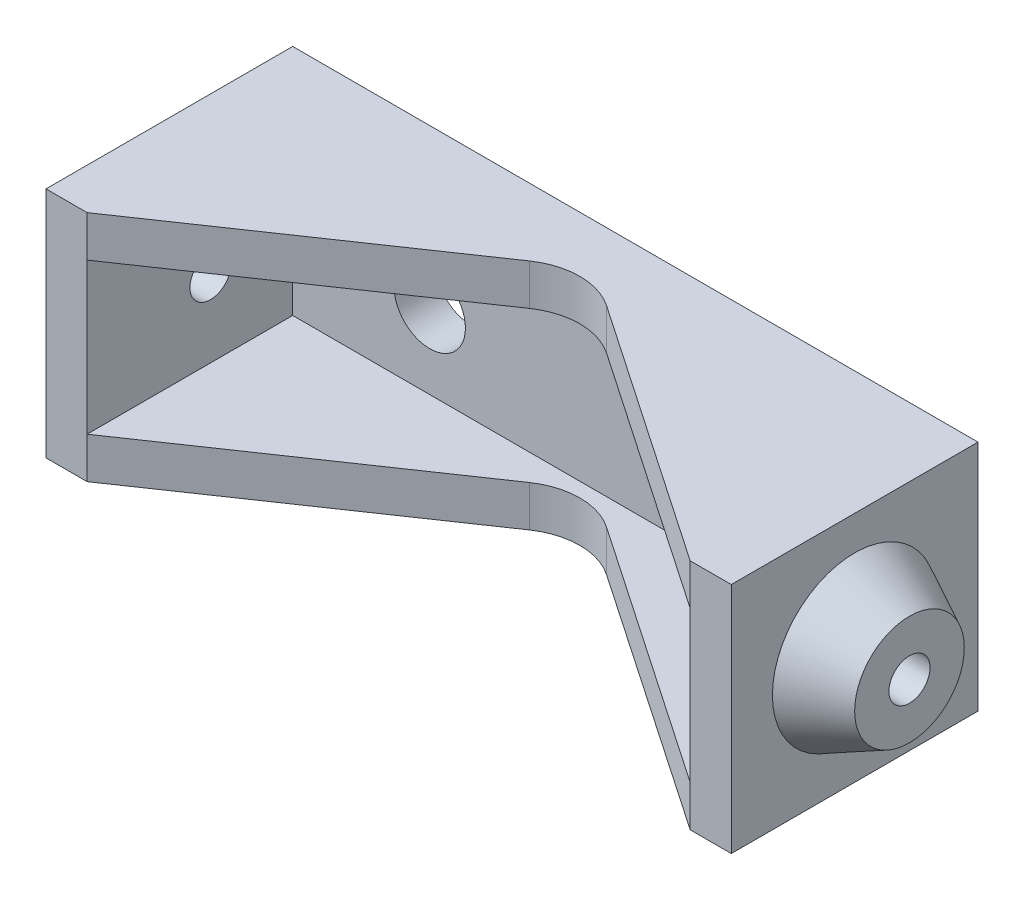
SolidWorks part; units mm, degrees
ref_plane "前视基准面" through (0, 0, 0) normal (0, 0, 1) x (1, 0, 0)
ref_plane "上视基准面" through (0, 0, 0) normal (0, 1, 0) x (1, 0, 0)
ref_plane "右视基准面" through (0, 0, 0) normal (1, 0, 0) x (0, 0, -1)
sketch "草图1" plane through (0, 0, 0) normal (0, 0, 1) x (1, 0, 0)
  line L1 (-25, -8.5) -> (25, -8.5)
  line L2 (-25, -8.5) -> (-25, 8.5)
  line L3 (-25, 8.5) -> (25, 8.5)
  line L4 (25, -8.5) -> (25, 8.5)
  line L5 (-25, -8.5) -> (25, 8.5) construction
  line L6 (-25, 8.5) -> (25, -8.5) construction
  point P0 (0, 0)
  dimension "D1" = 50
  dimension "D2" = 17
extrude "凸台-拉伸1" add sketch "草图1" along normal blind 18
sketch "草图2" plane through (0, 0, 18) normal (0, 0, 1) x (1, 0, 0)
  line L1 (-22, -5.5) -> (22, -5.5)
  line L2 (-22, -5.5) -> (-22, 5.5)
  line L3 (-22, 5.5) -> (22, 5.5)
  line L4 (22, -5.5) -> (22, 5.5)
  line L5 (-22, -5.5) -> (22, 5.5) construction
  line L6 (-22, 5.5) -> (22, -5.5) construction
  point P0 (0, 0)
  dimension "D1" = 44
  dimension "D2" = 11
extrude "切除-拉伸1" cut sketch "草图2" against normal blind 15
sketch "草图3" plane through (0, 8.5, 0) normal (0, 1, 0) x (1, 0, 0)
  line L1 (25, -18) -> (-25, -18) construction
  line L4 (2.8167, -4.9205) -> (22, -18)
  line L5 (-2.8167, -4.9205) -> (-22, -18)
  arc A0 (-2.8167, -4.9205) -> (2.8167, -4.9205) centre (0, -9.0516) cw
  dimension "D1" = 5
extrude "切除-拉伸2" cut sketch "草图3" against normal blind 17 and the other way through all flip side to cut
sketch "草图4" plane through (0, 0, 3) normal (0, 0, 1) x (1, 0, 0)
  circle A0 centre (-12, 0) radius 2.6
  circle A2 centre (12, 0) radius 2.6
extrude "切除-拉伸4" cut sketch "草图4" against normal blind 3
sketch "草图5" plane through (-25, 0, 0) normal (-1, 0, 0) x (0, 0, 1)
  circle A0 centre (9, 0) radius 1.5
  circle A1 centre (9, 0) radius 4
extrude "凸台-拉伸2" add sketch "草图5" along normal blind 4
sketch "草图6" plane through (25, 0, 0) normal (1, 0, 0) x (0, 0, -1)
  circle A0 centre (-9, 0) radius 1.5
  circle A1 centre (-9, 0) radius 4
extrude "凸台-拉伸3" add sketch "草图6" along normal blind 4
chamfer "倒角1" distance 2 distance2 4 2 edges at (25, 0, 13) (-25, 0, 5) first distance on face at (25, 0, 13) first distance on face at (-25, 0, 5)
sketch "草图7" plane through (-25, 0, 0) normal (-1, 0, 0) x (0, 0, 1)
  circle A0 centre (9, 0) radius 1.5
extrude "切除-拉伸5" cut sketch "草图7" against normal blind 50
